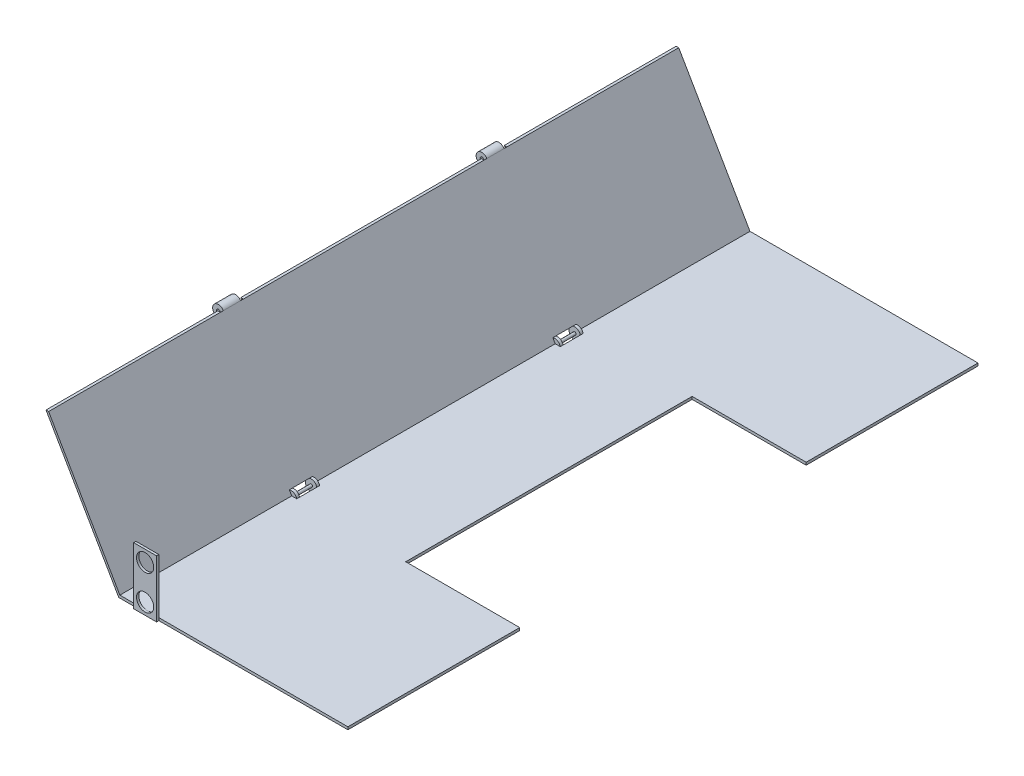
SolidWorks part; units mm, degrees
ref_plane "Front Plane" through (0, 0, 0) normal (0, 0, 1) x (1, 0, 0)
ref_plane "Top Plane" through (0, 0, 0) normal (0, 1, 0) x (1, 0, 0)
ref_plane "Right Plane" through (0, 0, 0) normal (1, 0, 0) x (0, 0, -1)
sketch "Sketch1" plane through (0, 0, 0) normal (0, 0, 1) x (1, 0, 0)
  line L0 (0, 0) -> (-63.5085, 110)
  line L1 (0, 0) -> (200, 0)
  line L2 (-63.5085, 110) -> (-61.2225, 110)
  line L3 (-61.2225, 110) -> (0.9662, 2.286)
  line L4 (0.9662, 2.286) -> (200, 2.286)
  line L5 (200, 2.286) -> (200, 0)
  dimension "D1" = 120
  dimension "D2" = 110
  dimension "D3" = 200
  dimension "D4" = 2.286
extrude "Boss-Extrude1" add sketch "Sketch1" along normal blind 550
sketch "Sketch2" plane through (0, 2.286, 0) normal (0, 1, 0) x (1, 0, 0)
  line L0 (200, -550) -> (200, 0) construction
  line L1 (200, -150) -> (100.4831, -150)
  line L2 (200, -150) -> (200, -400)
  line L3 (200, -400) -> (100.4831, -400)
  line L4 (100.4831, -150) -> (100.4831, -400)
  line L5 (200, 0) -> (0.9662, 0) construction
  point P6 (200, -275)
  point P7 (100.4831, 0)
  dimension "D1" = 250
extrude "Cut-Extrude1" cut sketch "Sketch2" against normal through all
sketch "Sketch4" plane through (0, 0, 150) normal (0, 0, 1) x (1, 0, 0)
  line L0 (0, 0) -> (200, 0) construction
  line L1 (0, 0) -> (200, 0)
  line L2 (200, 2.286) -> (0.9662, 2.286) construction
  line L3 (200, 2.286) -> (0.9662, 2.286)
  line L4 (0, 0) -> (0.9662, 2.286)
  circle A0 centre (0.4831, 1.143) radius 5
  circle A1 centre (0.4831, 1.143) radius 1.2409
  dimension "D1" = 10
extrude "Cut-Extrude2" cut sketch "Sketch4" along normal blind 20 contours A0
extrude "Boss-Extrude3" add sketch "Sketch4<3>" along normal blind 2.5 contours A0
sketch "Sketch4<3>" plane through (0, 0, 150) normal (0, 0, 1) x (1, 0, 0) same geometry as "Sketch4"
extrude "Boss-Extrude4" add sketch "Sketch4<5>" against normal blind 2.5 from offset 20 contours A0
sketch "Sketch4<5>" plane through (0, 0, 150) normal (0, 0, 1) x (1, 0, 0) same geometry as "Sketch4"
extrude "Boss-Extrude5" add sketch "Sketch4<7>" along normal blind 17.5 contours A1
sketch "Sketch4<7>" plane through (0, 0, 150) normal (0, 0, 1) x (1, 0, 0) same geometry as "Sketch4"
ref_plane "Plane2" through (0, 0, 275) normal (0, 0, 1) x (1, 0, 0)
mirror "Mirror1" about plane through (0, 0, 275) normal (0, 0, 1) of "Boss-Extrude5", "Boss-Extrude4", "Boss-Extrude3", "Cut-Extrude2"
sketch "Sketch5" plane through (0, 0, 550) normal (0, 0, 1) x (1, 0, 0)
  line L0 (0.9662, 2.286) -> (-61.2225, 110) construction
  line L1 (0.9662, 2.286) -> (-61.2225, 110)
  circle A0 centre (-65.5527, 107.5) radius 5
  circle A1 centre (-65.5527, 107.5) radius 1.5
  point P5 (-61.2225, 110)
  dimension "D1" = 10
  dimension "D2" = 3
extrude "Boss-Extrude6" add sketch "Sketch5" against normal blind 19.5 from offset 150 contours A0 | A1 offset against normal yes
extrude "Cut-Extrude5" cut sketch "Sketch5<4>" against normal blind 2.5 from offset 167.5 contours A0 offset against normal yes
sketch "Sketch5<4>" plane through (0, 0, 550) normal (0, 0, 1) x (1, 0, 0) same geometry as "Sketch5"
extrude "Cut-Extrude6" cut sketch "Sketch5<6>" against normal blind 2.5 from offset 150 contours A0 offset against normal yes
sketch "Sketch5<6>" plane through (0, 0, 550) normal (0, 0, 1) x (1, 0, 0) same geometry as "Sketch5"
mirror "Mirror2" about plane through (0, 0, 275) normal (0, 0, 1) of "Cut-Extrude6", "Cut-Extrude5", "Boss-Extrude6"
sketch "Sketch7" plane through (0, 0, 550) normal (0, 0, 1) x (1, 0, 0)
  line L0 (0, 0) -> (200, 0) construction
  line L1 (15, 0) -> (35, 0)
  line L2 (15, 0) -> (15, 50)
  line L3 (15, 50) -> (35, 50)
  line L4 (35, 0) -> (35, 50)
  line L5 (15, 20) -> (35, 0)
  line L6 (35, 50) -> (15, 30)
  circle A0 centre (25, 10) radius 7.5
  circle A1 centre (25, 40) radius 7.5
  line M1 (0, 0) -> (200, 0)
  line M3 (200, 2.286) -> (0.9662, 2.286)
  dimension "D4" = 15
  dimension "D1" = 15
  dimension "D2" = 20
  dimension "D3" = 20
  dimension "D5" = 30
  dimension "D6" = 20
extrude "Boss-Extrude7" add sketch "Sketch7" along normal blind 2 contours A0 L4 L3 M3 | A0 L2 M3 | L2 M3 M1 | L4 M3 | A1 L3 L2 region at (24.44, 1.1199, 550) region at (34.238, 1.524, 550) region at (15.2505, 11.143, 550) region at (27.1666, 25.1458, 550) region at (32.4517, 47.8517, 550)
